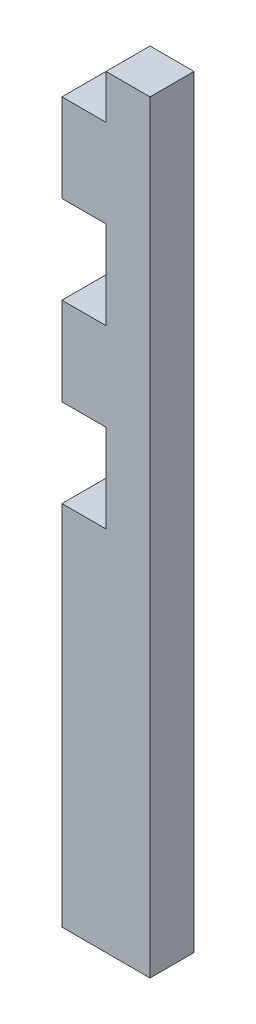
SolidWorks part; units mm, degrees
ref_plane "Front Plane" through (0, 0, 0) normal (0, 0, 1) x (1, 0, 0)
ref_plane "Top Plane" through (0, 0, 0) normal (0, 1, 0) x (1, 0, 0)
ref_plane "Right Plane" through (0, 0, 0) normal (1, 0, 0) x (0, 0, -1)
sketch "Sketch1" plane through (0, 0, 0) normal (0, 0, 1) x (1, 0, 0)
  line L3 (12, 0) -> (0, 0)
  line L4 (0, 0) -> (0, -50)
  line L5 (0, -50) -> (12, -50)
  line L6 (12, -50) -> (12, 0)
  line L9 (0, 0) -> (20, 0)
  line L26 (0, 0) -> (0, -50)
  line L28 (12, 0) -> (0, 0)
  line L29 (12, 0) -> (12, 54)
  line L30 (12, 54) -> (0, 54)
  line L31 (0, 0) -> (0, 54)
  dimension "D1" = 12
  dimension "D2" = 54
  dimension "D3" = 12
  dimension "D4" = 50
extrude "Boss-Extrude4" add sketch "Sketch1" along normal blind 6 contours L31 L3 region at (6, 27, 0)
extrude "Boss-Extrude5" add sketch "Sketch1<8>" along normal blind 6 contours L5 L6 L3 L4 region at (6, -25, 0)
sketch "Sketch1<8>" plane through (0, 0, 0) normal (0, 0, 1) x (1, 0, 0) same geometry as "Sketch1"
sketch "Sketch3" plane through (0, 0, 6) normal (0, 0, 1) x (1, 0, 0)
  line L1 (10, -40) -> (12, -40)
  line L2 (10, -40) -> (10, -50)
  line L3 (10, -50) -> (12, -50)
  line L4 (12, -40) -> (12, -50)
  line L5 (12, -50) -> (12, 54) construction
  dimension "D1" = 10
  dimension "D2" = 10
sketch "Sketch4" plane through (0, 0, 0) normal (0, 0, -1) x (-1, 0, 0)
  line L1 (0, 60) -> (-6, 60)
  line L2 (0, 60) -> (0, 48)
  line L3 (0, 48) -> (-6, 48)
  line L4 (-6, 60) -> (-6, 48)
  line L6 (-12, 54) -> (0, 54) construction
  line L7 (0, -50) -> (0, 54) construction
  line L8 (0, 36) -> (0, 24)
  line L9 (0, 36) -> (-6, 36)
  line L10 (-6, 36) -> (-6, 24)
  line L11 (0, 24) -> (-6, 24)
  line L12 (0, 12) -> (0, 0)
  line L13 (0, 12) -> (-6, 12)
  line L14 (-6, 12) -> (-6, 0)
  line L15 (0, 0) -> (-6, 0)
  dimension "D1" = 6
  dimension "D2" = 12
  dimension "D3" = 6
  dimension "D4" = 3
extrude "Cut-Extrude1" cut sketch "Sketch4" against normal up to next
